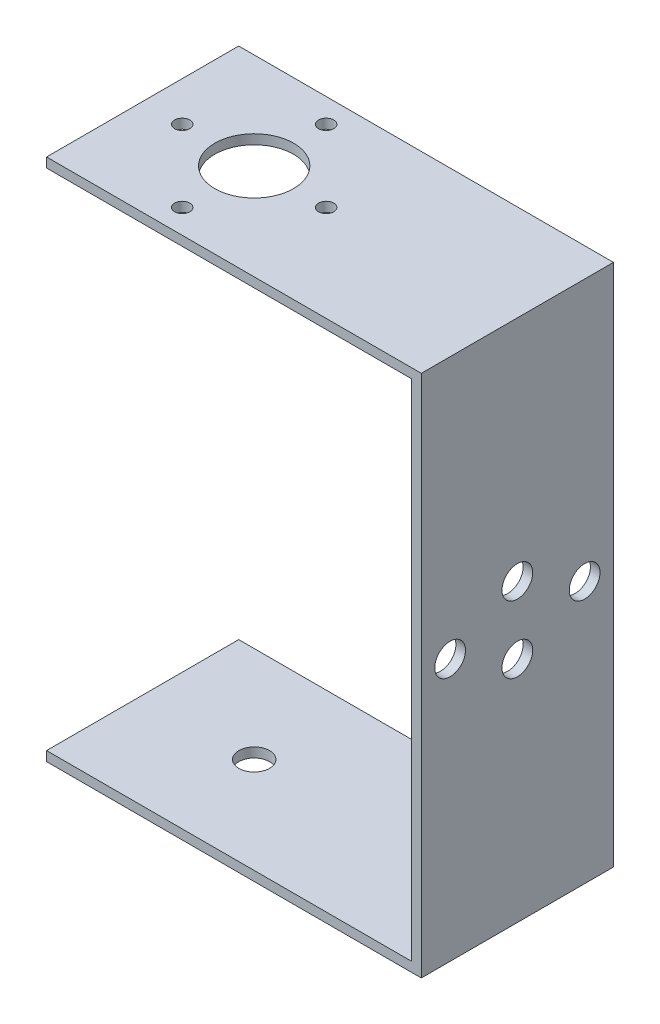
SolidWorks part; units mm, degrees
ref_plane "正面" through (0, 0, 0) normal (0, 0, 1) x (1, 0, 0)
ref_plane "平面" through (0, 0, 0) normal (0, 1, 0) x (1, 0, 0)
ref_plane "右側面" through (0, 0, 0) normal (1, 0, 0) x (0, 0, -1)
sketch "ｽｹｯﾁ1" plane through (0, 0, 0) normal (1, 0, 0) x (0, 0, -1)
  line L1 (0, 0) -> (20, 0)
  line L2 (0, 0) -> (0, 54.5)
  line L3 (0, 54.5) -> (20, 54.5)
  line L4 (20, 0) -> (20, 54.5)
extrude "ﾎﾞｽ - 押し出し1" add sketch "ｽｹｯﾁ1" along normal blind 1
sketch "ｽｹｯﾁ2" plane through (0, 0, 0) normal (-1, 0, 0) x (0, 0, 1)
  line L0 (0, 54.5) -> (0, 0) construction
  line L1 (-20, 54.5) -> (0, 54.5)
  line L2 (-20, 54.5) -> (-20, 53.5)
  line L3 (-20, 53.5) -> (0, 53.5)
  line L4 (0, 54.5) -> (0, 53.5)
extrude "ﾎﾞｽ - 押し出し2" add sketch "ｽｹｯﾁ2" along normal blind 38
sketch "ｽｹｯﾁ3" plane through (0, 0, 0) normal (-1, 0, 0) x (0, 0, 1)
  line L0 (-20, 0) -> (-20, 53.5) construction
  line L1 (0, 0) -> (-20, 0)
  line L2 (0, 0) -> (0, 1)
  line L3 (0, 1) -> (-20, 1)
  line L4 (-20, 0) -> (-20, 1)
extrude "ﾎﾞｽ - 押し出し3" add sketch "ｽｹｯﾁ3" along normal blind 38
sketch "ｽｹｯﾁ4" plane through (0, 54.5, 0) normal (0, 1, 0) x (1, 0, 0)
  circle A0 centre (-26.39, 10) radius 4.1
extrude "ｶｯﾄ - 押し出し1" cut sketch "ｽｹｯﾁ4" against normal blind 1
sketch "ｽｹｯﾁ5" plane through (0, 54.5, 0) normal (0, 1, 0) x (1, 0, 0)
  circle A0 centre (-33.88, 10) radius 0.79
extrude "ｶｯﾄ - 押し出し2" cut sketch "ｽｹｯﾁ5" against normal blind 1
sketch "ｽｹｯﾁ6" plane through (0, 54.5, 0) normal (0, 1, 0) x (1, 0, 0)
  circle A0 centre (-18.9, 10) radius 0.79
extrude "ｶｯﾄ - 押し出し3" cut sketch "ｽｹｯﾁ6" against normal blind 1
sketch "ｽｹｯﾁ7" plane through (0, 54.5, 0) normal (0, 1, 0) x (1, 0, 0)
  circle A0 centre (-26.39, 2.51) radius 0.79
extrude "ｶｯﾄ - 押し出し4" cut sketch "ｽｹｯﾁ7" against normal blind 1
sketch "ｽｹｯﾁ8" plane through (0, 54.5, 0) normal (0, 1, 0) x (1, 0, 0)
  circle A0 centre (-26.39, 17.49) radius 0.79
extrude "ｶｯﾄ - 押し出し5" cut sketch "ｽｹｯﾁ8" against normal blind 1
sketch "ｽｹｯﾁ9" plane through (0, 0, 0) normal (0, -1, 0) x (-1, 0, 0)
  circle A0 centre (26.39, 10) radius 1.6
extrude "ｶｯﾄ - 押し出し6" cut sketch "ｽｹｯﾁ9" against normal blind 1
sketch "ｽｹｯﾁ10" plane through (1, 0, 0) normal (1, 0, 0) x (0, 0, -1)
  circle A0 centre (17, 27.25) radius 1.6
extrude "ｶｯﾄ - 押し出し7" cut sketch "ｽｹｯﾁ10" against normal up to next
sketch "ｽｹｯﾁ11" plane through (1, 0, 0) normal (1, 0, 0) x (0, 0, -1)
  circle A0 centre (3, 27.25) radius 1.6
extrude "ｶｯﾄ - 押し出し8" cut sketch "ｽｹｯﾁ11" against normal up to next
sketch "ｽｹｯﾁ12" plane through (1, 0, 0) normal (1, 0, 0) x (0, 0, -1)
  circle A0 centre (10, 23.75) radius 1.6
extrude "ｶｯﾄ - 押し出し9" cut sketch "ｽｹｯﾁ12" against normal up to next
sketch "ｽｹｯﾁ14" plane through (1, 0, 0) normal (1, 0, 0) x (0, 0, -1)
  circle A0 centre (10, 30.75) radius 1.6
extrude "ｶｯﾄ - 押し出し10" cut sketch "ｽｹｯﾁ14" against normal up to next
